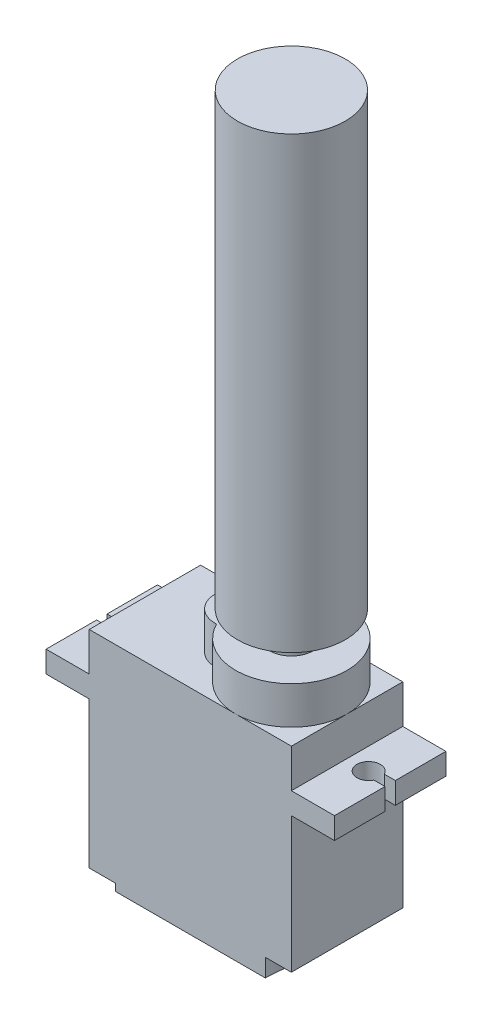
SolidWorks part; units mm, degrees
ref_plane "Alzado" through (0, 0, 0) normal (0, 0, 1) x (1, 0, 0)
ref_plane "Planta" through (0, 0, 0) normal (0, 1, 0) x (1, 0, 0)
ref_plane "Vista lateral" through (0, 0, 0) normal (1, 0, 0) x (0, 0, -1)
sketch "Croquis1" plane through (0, 0, 0) normal (0, 0, 1) x (1, 0, 0)
  line L0 (0, 11.9) -> (0, -11.9) construction
  line L4 (-11.25, -11.9) -> (-11.25, 11.9)
  line L5 (-11.25, 11.9) -> (11.25, 11.9)
  line L6 (-11.25, -11.9) -> (11.25, -11.9)
  line L7 (-16.05, 5.2) -> (-11.25, 5.2)
  line L8 (-16.05, 5.2) -> (-16.05, 7.6)
  line L9 (-16.05, 7.6) -> (-11.25, 7.6)
  line L10 (-11.25, 5.2) -> (-11.25, 7.6)
  line L11 (-16.05, 5.2) -> (-11.25, 7.6) construction
  line L12 (-16.05, 7.6) -> (-11.25, 5.2) construction
  line L14 (11.25, -11.9) -> (11.25, 11.9)
  line L16 (16.05, 7.6) -> (11.25, 7.6)
  line L17 (11.25, 5.2) -> (11.25, 7.6)
  line L18 (16.05, 5.2) -> (11.25, 5.2)
  line L19 (16.05, 5.2) -> (16.05, 7.6)
  point P0 (0, 0)
  point P2 (-11.25, 0)
  point P6 (-13.65, 6.4)
  dimension "D1" = 23.8
  dimension "D2" = 2.4
  dimension "D3" = 22.5
  dimension "D4" = 4.8
  dimension "D5" = 4.3
extrude "Saliente-Extruir1" add sketch "Croquis1" along normal mid plane 12.4 contours L9 L8 L7 L4 | L6 L14 L5 L4 | L18 L19 L16 L14 region at (0, 0, 0) region at (-13.65, 6.4, 0) region at (13.65, 6.4, 0)
sketch "Croquis2" plane through (0, 11.9, 0) normal (0, 1, 0) x (1, 0, 0)
  line L0 (-11.25, 6.2) -> (11.25, 6.2) construction
  line L1 (-11.25, -6.2) -> (11.25, -6.2) construction
  line L2 (11.25, -6.2) -> (11.25, 6.2) construction
  line L3 (-0.65, 0) -> (-3.45, 0) construction
  arc A0 (-0.4842, -2.7951) -> (-0.4842, 2.7951) centre (5.05, 0) ccw
  arc A1 (-0.4842, 2.7951) -> (-0.4842, -2.7951) centre (-0.65, 0) ccw
  dimension "D2" = 5.6
  dimension "D1" = 14.7
extrude "Saliente-Extruir2" add sketch "Croquis2" along normal blind 4.2
sketch "Croquis3" plane through (0, 7.6, 0) normal (0, 1, 0) x (1, 0, 0)
  line L0 (0, -6.2) -> (0, 6.2) construction
  line L1 (-11.25, -6.2) -> (5.05, -6.2) construction
  line L2 (-11.25, 6.2) -> (5.05, 6.2) construction
  line L3 (16.05, 0.575) -> (14.8159, 0.575)
  line L4 (16.05, -6.2) -> (16.05, 6.2) construction
  line L5 (16.05, -0.575) -> (14.8159, -0.575)
  line L6 (16.05, 0.575) -> (16.05, -0.575)
  line L7 (-16.05, 0.575) -> (-14.8159, 0.575)
  line L8 (-16.05, 0.575) -> (-16.05, -0.575)
  line L9 (-16.05, -0.575) -> (-14.8159, -0.575)
  arc A1 (14.8159, 0.575) -> (14.8159, -0.575) centre (13.65, 0) ccw
  arc A2 (-14.8159, 0.575) -> (-14.8159, -0.575) centre (-13.65, 0) cw
  point P16 (16.05, 0)
  point P18 (16.05, 0)
  dimension "D2" = 2.6
  dimension "D1" = 1.15
  dimension "D3" = 2.4
extrude "Cortar-Extruir1" cut sketch "Croquis3" against normal up to next
sketch "Croquis4" plane through (0, -11.9, 0) normal (0, -1, 0) x (1, 0, 0)
  line L0 (0, 6.2) -> (0, -6.2) construction
  line L1 (-11.25, 0) -> (11.25, 0) construction
  line L2 (-11.25, 3.3) -> (-11.25, 6.2)
  line L3 (-11.25, 6.2) -> (-8.35, 6.2)
  line L4 (-11.25, -6.2) -> (11.25, -6.2)
  line L5 (11.25, -6.2) -> (11.25, 6.2)
  line L6 (11.25, 6.2) -> (-11.25, 6.2)
  line L7 (-11.25, 6.2) -> (-11.25, -6.2)
  line L8 (-11.25, -6.2) -> (11.25, -6.2)
  line L9 (11.25, -6.2) -> (11.25, 6.2)
  line L10 (11.25, 6.2) -> (-11.25, 6.2)
  line L11 (-11.25, 6.2) -> (-11.25, -6.2)
  line L12 (-11.25, -3.3) -> (-11.25, -6.2)
  line L13 (-11.25, -6.2) -> (-8.35, -6.2)
  line L14 (11.25, 3.3) -> (11.25, 6.2)
  line L15 (11.25, 6.2) -> (8.35, 6.2)
  line L16 (11.25, -3.3) -> (11.25, -6.2)
  line L17 (11.25, -6.2) -> (8.35, -6.2)
  line L18 (8.35, 6.2) -> (8.35, -6.2)
  line L19 (9.75, -1.875) -> (11.25, -1.875)
  line L20 (9.75, -1.875) -> (9.75, 1.875)
  line L21 (9.75, 1.875) -> (11.25, 1.875)
  line L22 (11.25, -1.875) -> (11.25, 1.875)
  line L23 (9.75, -1.875) -> (11.25, 1.875) construction
  line L24 (9.75, 1.875) -> (11.25, -1.875) construction
  arc A0 (-8.35, 6.2) -> (-11.25, 3.3) centre (-11.25, 6.2) cw
  arc A1 (-8.35, -6.2) -> (-11.25, -3.3) centre (-11.25, -6.2) ccw
  arc A2 (8.35, 6.2) -> (11.25, 3.3) centre (11.25, 6.2) ccw
  arc A3 (8.35, -6.2) -> (11.25, -3.3) centre (11.25, -6.2) cw
  point P17 (10.5, 0)
  dimension "D2" = 2.9
  dimension "D3" = 3.75
  dimension "D4" = 1.5
  dimension "D1" = 0
extrude "Cortar-Extruir3" cut sketch "Croquis4" against normal blind 0.8 contours A0 L16 L4 | L17 A1 L11 region at (-10.0192, -11.9, 4.9692) region at (-10.0192, -11.9, -4.9692)
extrude "Cortar-Extruir4" cut sketch "Croquis4<5>" against normal blind 2 contours L16 A2 L9 | L21 L20 L19 A3 | A3 L17 region at (10.0192, -11.9, 4.9692) region at (10.0192, -11.9, -4.9692) region at (10.5, -11.9, 0)
sketch "Croquis4<5>" plane through (0, -11.9, 0) normal (0, -1, 0) x (1, 0, 0) same geometry as "Croquis4"
sketch "Croquis6" plane through (0, 0, -6.2) normal (0, 0, -1) x (-1, 0, 0)
  line L0 (-11.25, -9.9) -> (-8.35, -11.9)
  line L1 (-8.35, -11.9) -> (-11.25, -11.9)
  line L2 (-11.25, -11.9) -> (-11.25, -9.9)
extrude "Cortar-Extruir5" cut sketch "Croquis6" against normal through all
sketch "Croquis7" plane through (0, 16.1, 0) normal (0, 1, 0) x (1, 0, 0)
  circle A0 centre (5.05, 0) radius 2.425
  circle A1 centre (5.05, 0) radius 0.875
  dimension "D1" = 4.85
  dimension "D2" = 1.55
extrude "Saliente-Extruir4" add sketch "Croquis7" along normal blind 2.85
sketch "Sketch1" plane through (0, 18.95, 0) normal (0, 1, 0) x (1, 0, 0)
  circle A0 centre (5.05, 0) radius 6
extrude "Boss-Extrude1" add sketch "Sketch1" along normal blind 50
